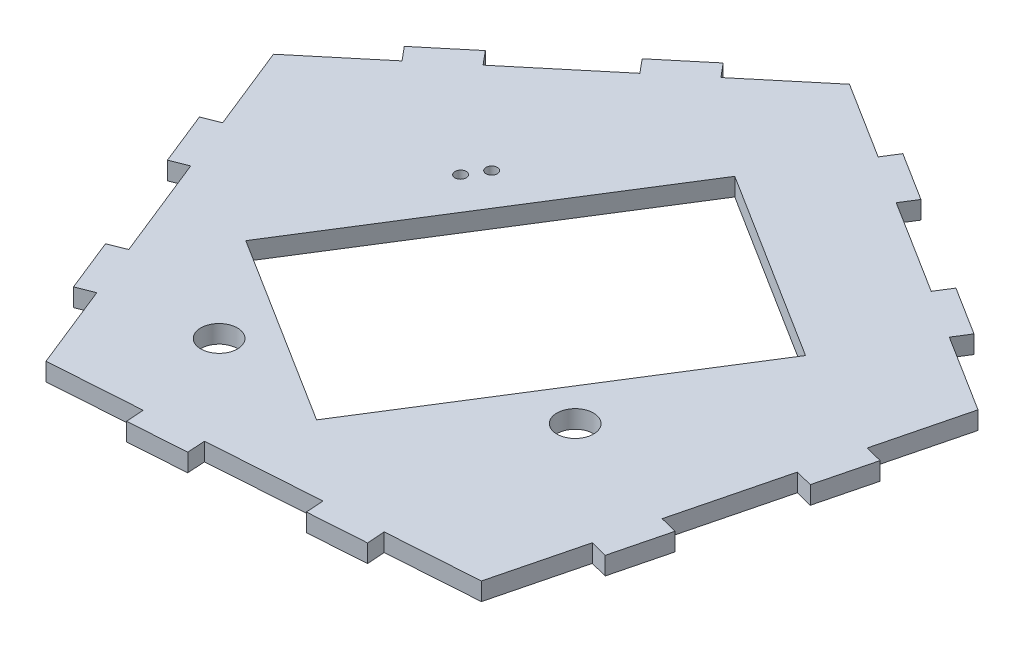
SolidWorks part; units mm, degrees
ref_plane "Front Plane" through (0, 0, 0) normal (0, 0, 1) x (1, 0, 0)
ref_plane "Top Plane" through (0, 0, 0) normal (0, 1, 0) x (1, 0, 0)
ref_plane "Right Plane" through (0, 0, 0) normal (1, 0, 0) x (0, 0, -1)
sketch "Sketch1" plane through (0, 0, 0) normal (0, 1, 0) x (1, 0, 0)
  line L1 (-59.9258, 15.1181) -> (-32.8962, -52.3211)
  line L2 (-32.8962, -52.3211) -> (39.5948, -47.4543)
  line L3 (39.5948, -47.4543) -> (57.3672, 22.9927)
  line L4 (57.3672, 22.9927) -> (-4.14, 61.6646)
  line L5 (-4.14, 61.6646) -> (-59.9258, 15.1181)
  circle A0 centre (0, 0) radius 50 construction
  dimension "D1" = 100
extrude "Boss-Extrude1" add sketch "Sketch1" along normal blind 3.18
ref_axis "Axis" through (0, 3.339, 0) along (0, -1, 0)
sketch "Axis Check" plane through (0, 3.18, 0) normal (0, 1, 0) x (1, 0, 0)
  line L0 (3.3493, -49.8877) -> (-4.14, 61.6646) construction
  line L1 (-32.8962, -52.3211) -> (39.5948, -47.4543) construction
  line L2 (57.3672, 22.9927) -> (-46.411, -18.6015) construction
  line L3 (-59.9258, 15.1181) -> (-32.8962, -52.3211) construction
  line L4 (-32.0329, 38.3913) -> (39.5948, -47.4543) construction
  line L5 (-4.14, 61.6646) -> (-59.9258, 15.1181) construction
  line L6 (-59.9258, 15.1181) -> (48.481, -12.2308) construction
  line L7 (39.5948, -47.4543) -> (57.3672, 22.9927) construction
  line L8 (-32.8962, -52.3211) -> (26.6136, 42.3287) construction
  line L9 (57.3672, 22.9927) -> (-4.14, 61.6646) construction
sketch "Sketch2" plane through (0, 0, 0) normal (0, -1, 0) x (1, 0, 0)
  line L0 (-53.8107, 0.1392) -> (-50.859, -1.0438)
  line L1 (-53.8107, 0.1392) -> (-50.1723, 9.2172)
  line L2 (-50.859, -1.0438) -> (-47.2205, 8.0342)
  line L3 (-50.1723, 9.2172) -> (-47.2205, 8.0342)
  line L4 (-59.9258, -15.1181) -> (-32.8962, 52.3211) construction
  line L5 (-42.6498, 27.9858) -> (-39.0113, 37.0638)
  line L6 (-42.6498, 27.9858) -> (-39.6981, 26.8028)
  line L7 (-39.0113, 37.0638) -> (-36.0596, 35.8808)
  line L8 (-39.6981, 26.8028) -> (-36.0596, 35.8808)
  line L9 (-46.411, 18.6015) -> (-19.2439, 7.7129) construction
  line L10 (-40.8306, 32.5248) -> (-37.8788, 31.3418) construction
  dimension "D1" = 3.18
  dimension "D2" = 9.78
  dimension "D3" = 10.11
extrude "Cut F" [suppressed] cut sketch "Sketch2" against normal through all
sketch "Sketch4" plane through (0, 3.18, 0) normal (0, 1, 0) x (1, 0, 0)
  line L9 (26.6136, 42.3287) -> (-26.6136, -42.3287) construction
  line L10 (57.3672, 22.9927) -> (-4.14, 61.6646) construction
  line L11 (-33.698, -16.0216) -> (-0.1649, 37.3125)
  line L12 (-33.698, -16.0216) -> (0.1649, -37.3125)
  line L13 (-0.1649, 37.3125) -> (33.698, 16.0216)
  line L14 (0.1649, -37.3125) -> (33.698, 16.0216)
  line L15 (-33.698, -16.0216) -> (33.698, 16.0216) construction
  line L16 (-0.1649, 37.3125) -> (0.1649, -37.3125) construction
  line L20 (0, 0) -> (39.0006, -24.5211) construction
  circle A0 centre (-21.0248, -33.4396) radius 3.25
  circle A1 centre (23.7041, -14.9036) radius 3.25
  point P5 (0, 0)
  point P6 (-21.0248, -33.4396)
  dimension "D3" = 6.5
  dimension "D1" = 40
  dimension "D2" = 63
  dimension "D4" = 8
  dimension "D5" = 8
extrude "Top Cut" cut sketch "Sketch4" against normal blind 10
sketch "Sketch7" plane through (0, 3.18, 0) normal (0, 1, 0) x (1, 0, 0)
  line L0 (0, 0) -> (26.6136, 42.3287) construction
  line L1 (57.3672, 22.9927) -> (-4.14, 61.6646) construction
  line L2 (1.0645, 1.6931) -> (-22.6395, 16.5968) construction
  line L3 (-6.1086, 1.4782) -> (-24.7686, 13.2105) construction
  line L5 (-0.1649, 37.3125) -> (-33.698, -16.0216) construction
  circle A0 centre (-22.6395, 16.5968) radius 1
  circle A1 centre (-24.7686, 13.2105) radius 1
  dimension "D5" = 2
  dimension "D1" = 4
  dimension "D2" = 2
  dimension "D3" = 8
  dimension "D4" = 8
extrude "Top Cut 2" cut sketch "Sketch7" against normal through all
sketch "Sketch8" [suppressed] plane through (0, 3.18, 0) normal (0, 1, 0) x (1, 0, 0)
  line L0 (3.3493, -49.8877) -> (-4.14, 61.6646) construction
  line L5 (-32.8962, -52.3211) -> (39.5948, -47.4543) construction
  line L6 (-17.9455, -31.2723) -> (21.9647, -28.5929)
  line L11 (-17.9455, -31.2723) -> (-21.9647, 28.5929)
  line L12 (21.9647, -28.5929) -> (17.9455, 31.2723)
  line L13 (-21.9647, 28.5929) -> (17.9455, 31.2723)
  point P4 (1.4955, -22.2759)
  dimension "D1" = 60
  dimension "D2" = 40
  dimension "D3" = 20
extrude "Bottom Cut" [suppressed] cut sketch "Sketch8" against normal blind 10
sketch "Sketch9" [suppressed] plane through (0, 3.18, 0) normal (0, 1, 0) x (1, 0, 0)
  line L0 (19.9551, 1.3397) -> (-19.9551, -1.3397) construction
  line L1 (21.9647, -28.5929) -> (17.9455, 31.2723) construction
  line L2 (-21.9647, 28.5929) -> (-17.9455, -31.2723) construction
  line L3 (-19.9551, -1.3397) -> (-44.4689, -2.9855) construction
  line L4 (19.9551, 1.3397) -> (42.6839, 2.8657) construction
  line L5 (-32.8962, -52.3211) -> (39.5948, -47.4543) construction
  line L6 (-29.6051, -6.8886) -> (-32.3788, -7.0748)
  line L7 (-29.6051, -6.8886) -> (-30.2602, 2.8694)
  line L8 (-30.2602, 2.8694) -> (-33.0339, 2.6832)
  line L9 (-32.3788, -7.0748) -> (-33.0339, 2.6832)
  line L10 (-29.6051, -6.8886) -> (-33.0339, 2.6832) construction
  line L11 (-30.2602, 2.8694) -> (-32.3788, -7.0748) construction
  line L12 (33.0339, -2.6832) -> (30.2602, -2.8694)
  line L13 (33.0339, -2.6832) -> (32.3788, 7.0748)
  line L14 (32.3788, 7.0748) -> (29.6051, 6.8886)
  line L15 (30.2602, -2.8694) -> (29.6051, 6.8886)
  line L16 (33.0339, -2.6832) -> (29.6051, 6.8886) construction
  line L17 (32.3788, 7.0748) -> (30.2602, -2.8694) construction
  line L18 (-32.8962, -52.3211) -> (39.5948, -47.4543) construction
  point P6 (-31.3195, -2.1027)
  point P13 (31.3195, 2.1027)
  dimension "D1" = 9.78
  dimension "D4" = 9.78
  dimension "D5" = 10
  dimension "D6" = 10
  dimension "D3" = 2.78
  dimension "D2" = 2.78
extrude "Battery Holder Cut" [suppressed] cut sketch "Sketch9" against normal blind 3.18
sketch "Sketch3" plane through (0, 3.18, 0) normal (0, 1, 0) x (1, 0, 0)
  line L0 (0, 0) -> (-40.9819, 49.1167) construction
  line L1 (-49.5112, 27.9494) -> (-45.4366, 23.066)
  line L3 (-45.4366, 23.066) -> (-37.5894, 29.6135)
  line L4 (-41.664, 34.4969) -> (-37.5894, 29.6135)
  line L5 (-4.14, 61.6646) -> (-59.9258, 15.1181) construction
  line L6 (-71.9961, 5.0469) -> (-69.9588, 2.6052)
  line L7 (-71.9961, 5.0469) -> (-47.4739, 25.5077)
  line L14 (-26.4764, 47.1691) -> (-22.4018, 42.2857)
  line L16 (-22.4018, 42.2857) -> (-14.5546, 48.8333)
  line L17 (-18.6292, 53.7166) -> (-14.5546, 48.8333)
  line L18 (-42.539, 27.5695) -> (-41.513, 26.3398) construction
  line L19 (-49.5112, 27.9494) -> (-41.664, 34.4969)
  line L21 (-26.4764, 47.1691) -> (-18.6292, 53.7166)
  line L22 (-16.5919, 51.275) -> (4.7866, 69.1127)
  line L23 (-39.6267, 32.0552) -> (-24.4391, 44.7274)
  line M18 (-4.14, 61.6646) -> (-59.9258, 15.1181)
  dimension "D1" = 3.18
  dimension "D2" = 10.22
  dimension "D3" = 9.89
  dimension "D4" = 100
extrude "Extrude M" add sketch "Sketch3" against normal up to surface (3.18 mm away) contours L21 L14 L7 L17 | L19 L1 L4 M18 region at (-44.5689, 3.18, -30.0023) region at (-21.5341, 3.18, -49.222) up to face at (-22.6395, 0, -15.5968)
pattern_circular "Circle F" [suppressed] count 5 over 360 about axis through (0, 3.339, 0) along (0, -1, 0) of bodies 173
pattern_circular "Circle M" count 5 over 360 about axis through (0, 3.339, 0) along (0, -1, 0) of "Extrude M"
pattern_circular "Circle Side F" [suppressed] count 5 over 360 about axis through (0, 3.339, 0) along (0, -1, 0) of bodies 173
pattern_circular "Circle Side M" [suppressed] count 5 over 360 about axis through (0, 3.339, 0) along (0, -1, 0) of bodies 168
equation "\"kerf\"= .22mm"
equation "\"tabWidthF\"= 10 - \"kerf\""
equation "\"tabThickness\"= 3.18"
equation "\"D1@Sketch2\"=\"tabThickness\""
equation "\"tabWidthM\"= 10 + \"kerf\""
equation "\"halfkerf\"= \"kerf\" / 2.00mm"
equation "\"D1@Sketch9\"=\"tabWidthF\""
equation "\"D4@Sketch9\"=\"tabWidthF\""
equation "\"D1@Battery Holder Cut\" = \"tabThickness\""
equation "\"tabLength\" = \"kerf\" + 12"
